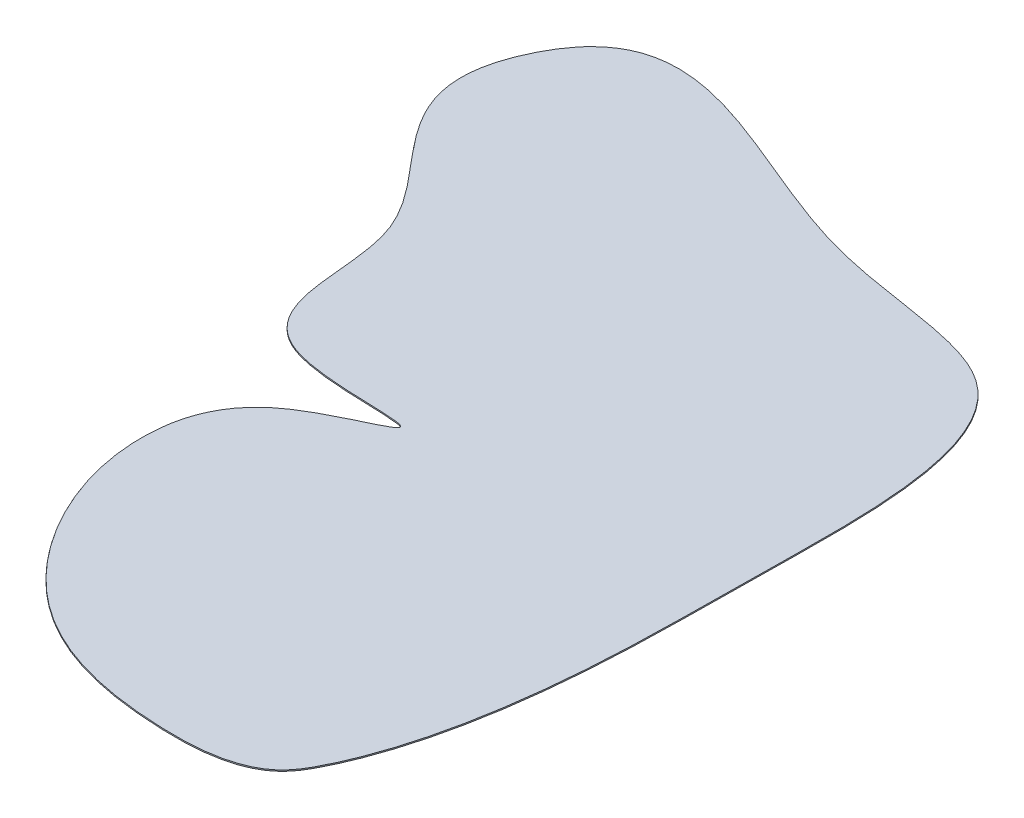
SolidWorks part; units mm, degrees
ref_plane "Front Plane" through (0, 0, 0) normal (0, 0, 1) x (1, 0, 0)
ref_plane "Top Plane" through (0, 0, 0) normal (0, 1, 0) x (1, 0, 0)
ref_plane "Right Plane" through (0, 0, 0) normal (1, 0, 0) x (0, 0, -1)
sketch "Sketch2" plane through (0, 0, 0) normal (0, 1, 0) x (1, 0, 0)
  line L1 (0, 0) -> (2743.2, 0)
  line L2 (0, 0) -> (0, -2743.2)
  line L3 (0, -2743.2) -> (2743.2, -2743.2)
  line L4 (2743.2, 0) -> (2743.2, -2743.2)
extrude "Boss-Extrude5" add sketch "Sketch2" along normal blind 2.54
sketch "Sketch4" plane through (0, 2.54, 0) normal (0, 1, 0) x (1, 0, 0)
  spline S0 degree 3 poles (912.5851, -1380.7074) (1381.1906, -1433.3821) (1879.5356, -1554.1962) (2340.6315, -1380.7074) knots 0 0 0 0 1 1 1 1
  spline S1 degree 3 poles (508.2148, -36.4494) (1278.1428, 110.5507) (1893.8971, -792.3816) (2340.6315, -1245.9173) knots 0 0 0 0 1 1 1 1
  spline S2 degree 2 poles (2340.6315, -1245.9173) (2450.1822, -1317.6681) (2340.6315, -1380.7074) knots 0 0 0 1 1 1
  spline S3 degree 2 poles (508.2148, -36.4494) (312.8785, -166.8791) (709.473, -780.8158) (756.1357, -1121.0937) (912.5851, -1380.7074) knots 0 0 0 0.294459 0.556343 1 1 1
  spline S4 degree 3 poles (1313.1183, -1433.2036) (1097.5204, -1463.953) (773.7784, -1944.1304) (1038.9673, -2482.472) (1775.7599, -2805.8672) (1973.2946, -2464.0408) (2375.0433, -2093.123) (2340.6315, -1380.7074) knots 0 0 0 0 0.213912 0.489653 0.685703 0.807002 1 1 1 1
sketch "Sketch5" plane through (0, 2.54, 0) normal (0, 1, 0) x (1, 0, 0)
  spline S0 degree 3 poles (1381.3756, -263.9505) (648.1941, 291.037) (273.3071, -491.0258) (878.115, -756.9647) (663.6876, -1474.9566) (1518.0338, -1382.9184) (985.0242, -1563.1188) (841.4333, -1982.3187) (1137.3701, -2567.7038) (1643.589, -2719.5859) (2078.1199, -2695.3967) (2253.6418, -2382.1782) (2342.36, -1856.4937) (2333.5656, -1207.2949) (2374.3537, -218.6699) (1381.3756, -263.9505) (648.1941, 291.037) (273.3071, -491.0258) knots -0.289077 -0.180775 -0.110557 0 0.021292 0.117399 0.193525 0.246711 0.285262 0.327734 0.420663 0.498327 0.542346 0.55612 0.63606 0.710923 0.819225 0.889443 1 1.021292 1.117399 1.193525 only from (508.2148, -36.4494) to (508.2148, -36.4494)
  spline S1 degree 2 poles (508.2148, -36.4494) (312.8785, -166.8791) (709.473, -780.8158) (756.1357, -1121.0937) (912.5851, -1380.7074) knots 0 0 0 0.294459 0.556343 1 1 1 construction
extrude "Boss-Extrude6" add sketch "Sketch5" along normal blind 1.5875 and the other way blind 1.5875
extrude "Cut-Extrude1" cut sketch "Sketch5<2>" against normal through all flip side to cut
sketch "Sketch5<2>" plane through (0, 2.54, 0) normal (0, 1, 0) x (1, 0, 0) same geometry as "Sketch5"
sketch "Sketch7" plane through (0, 4.1275, 0) normal (0, 1, 0) x (1, 0, 0)
  line L0 (2343.1267, -1039.1073) -> (752.5972, -1039.1073) construction
  line L1 (402.8731, 71.8636) -> (2343.1267, 71.8636) construction
  line L2 (402.8731, 71.8636) -> (402.8731, -2701.1548) construction
  line L3 (402.8731, -2701.1548) -> (2343.1267, -2701.1548) construction
  line L4 (2343.1267, 71.8636) -> (2343.1267, -2701.1548) construction
  spline S0 degree 3 poles (1381.3756, -263.9505) (648.1941, 291.037) (273.3071, -491.0258) (878.115, -756.9647) (663.6876, -1474.9566) (1518.0338, -1382.9184) (985.0242, -1563.1188) (841.4333, -1982.3187) (1137.3701, -2567.7038) (1643.589, -2719.5859) (2078.1199, -2695.3967) (2253.6418, -2382.1782) (2342.36, -1856.4937) (2333.5656, -1207.2949) (2374.3537, -218.6699) (1381.3756, -263.9505) (648.1941, 291.037) (273.3071, -491.0258) knots -0.289077 -0.180775 -0.110557 0 0.021292 0.117399 0.193525 0.246711 0.285262 0.327734 0.420663 0.498327 0.542346 0.55612 0.63606 0.710923 0.819225 0.889443 1 1.021292 1.117399 1.193525 only from (508.2148, -36.4494) to (508.2148, -36.4494) construction
